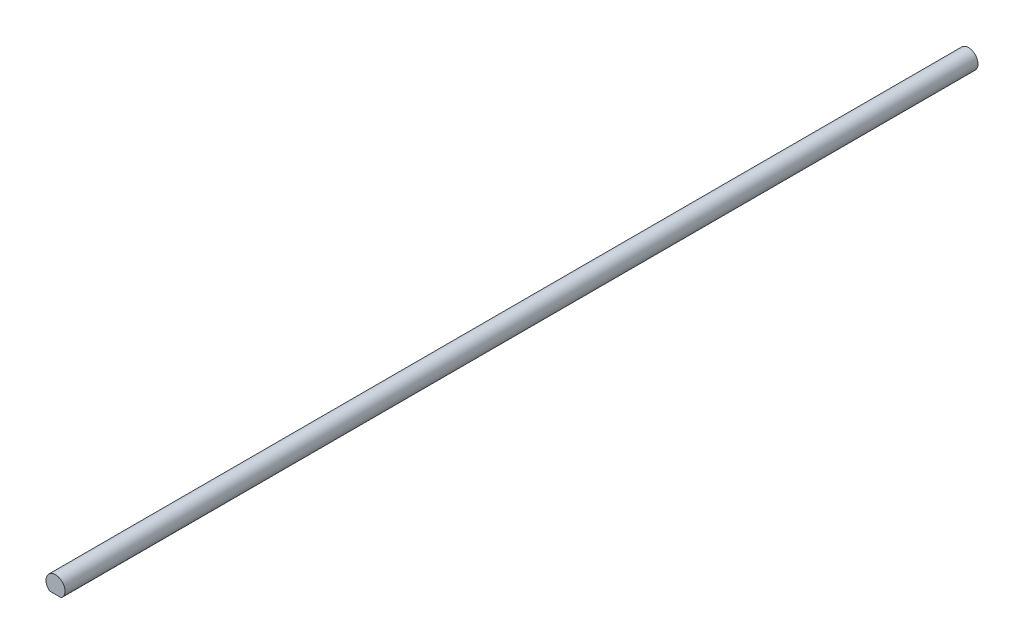
SolidWorks part; units mm, degrees
ref_plane "Front Plane" through (0, 0, 0) normal (0, 0, 1) x (1, 0, 0)
ref_plane "Top Plane" through (0, 0, 0) normal (0, 1, 0) x (1, 0, 0)
ref_plane "Right Plane" through (0, 0, 0) normal (1, 0, 0) x (0, 0, -1)
sketch "Sketch1" plane through (0, 0, 0) normal (0, 0, 1) x (1, 0, 0)
  line L0 (-1.905, -2.54) -> (1.905, -2.54)
  line L1 (0, 3.175) -> (0, -2.54) construction
  circle A0 centre (0, 0) radius 3.175
  dimension "D1" = 6.35
  dimension "D2" = 5.715
extrude "Boss-Extrude1" add sketch "Sketch1" along normal blind 152.4 and the other way blind 152.4 contours L1 A0 L0 | A0 L1 L0 region at (-1.3817, 0.1535, 0) region at (1.3817, 0.1535, 0)
